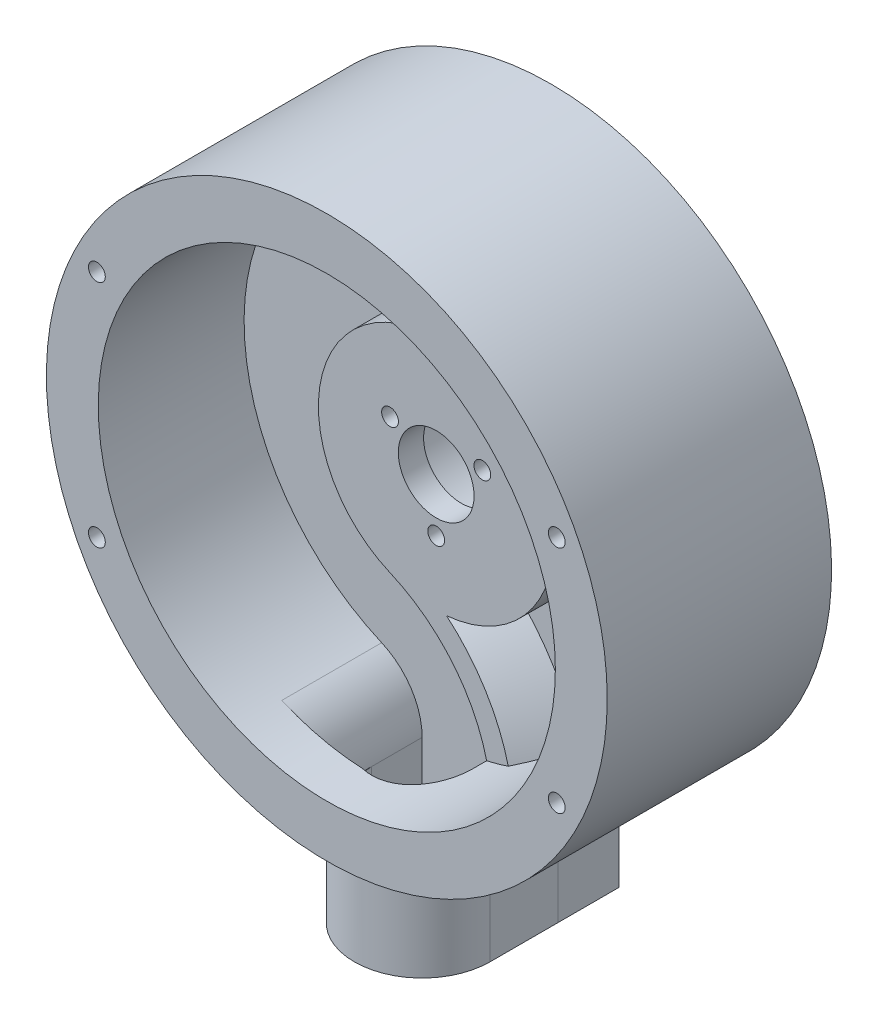
SolidWorks part; units mm, degrees
ref_plane "前视基准面" through (0, 0, 0) normal (0, 0, 1) x (1, 0, 0)
ref_plane "上视基准面" through (0, 0, 0) normal (0, 1, 0) x (1, 0, 0)
ref_plane "右视基准面" through (0, 0, 0) normal (1, 0, 0) x (0, 0, -1)
other "Configuration Table"
sketch "草图1" plane through (0, 0, 0) normal (0, 0, 1) x (1, 0, 0)
  circle A0 centre (0, 0) radius 21
  circle A1 centre (0, 0) radius 12.6
  dimension "D1" = 42
  dimension "D2" = 25.2
extrude "凸台-拉伸1" add sketch "草图1" along normal blind 7
sketch "草图3" plane through (0, 0, 0) normal (0, 0, -1) x (-1, 0, 0)
  circle A0 centre (0, 0) radius 50
  circle A2 centre (0, 0) radius 21
  circle A3 centre (0, 0) radius 21
  dimension "D2" = 100
  dimension "D1" = 0
extrude "凸台-拉伸3" add sketch "草图3" against normal blind 3
sketch "草图4" plane through (0, 0, 3) normal (0, 0, 1) x (1, 0, 0)
  circle A0 centre (0, 0) radius 40.75
  circle A1 centre (0, 0) radius 50
  circle A2 centre (0, 0) radius 50
  dimension "D2" = 81.5
  dimension "D1" = 0
extrude "凸台-拉伸4" add sketch "草图4" along normal blind 26
sketch "草图5" plane through (0, 0, 7) normal (0, 0, 1) x (1, 0, 0)
  circle A1 centre (0, 0) radius 6.75
  circle A3 centre (0, 0) radius 21
  circle A4 centre (0, 0) radius 21
  dimension "D1" = 13.5
  dimension "D2" = 0
extrude "凸台-拉伸5" add sketch "草图5" along normal blind 2.5
sketch "草图6" plane through (0, 0, 3) normal (0, 0, 1) x (1, 0, 0)
  arc A0 (-8.2952, -19.2922) -> (9, -39.7437) centre (-20.1456, -46.8525) cw
  circle A1 centre (0, 0) radius 21 construction
  circle A2 centre (0, 0) radius 21 construction
  circle A3 centre (0, 0) radius 40.75 construction
  arc A4 (0.3602, -20.9969) -> (11.9001, -38.9737) centre (-20.1456, -46.8525) cw
  circle A5 centre (0, 0) radius 40.75 construction
  circle A6 centre (0, 0) radius 40.75
  circle A7 centre (0, 0) radius 21
  circle A8 centre (0, 0) radius 21
  circle M2 centre (0, 0) radius 21
  circle M3 centre (0, 0) radius 40.75
  dimension "D2" = 30
  dimension "D3" = 33
  dimension "D1" = 9
  dimension "D4" = 0
extrude "凸台-拉伸6" add sketch "草图6" along normal blind 6.5 contours A4 A0 M2 M3 region at (4.9964, -29.2129, 3)
ref_plane "基准面1" through (0, -68, 0) normal (0, 1, 0) x (1, 0, 0)
sketch "草图7" plane through (0, -68, 0) normal (0, 1, 0) x (1, 0, 0)
  line L0 (50, 0) -> (-50, 0) construction
  line L1 (-9, -12) -> (9, -12)
  line L2 (-9, -12) -> (-9, -3)
  line L3 (-9, -3) -> (9, -3)
  line L4 (9, -12) -> (9, -3)
  line L5 (-9, -12) -> (9, -3) construction
  line L6 (-9, -3) -> (9, -12) construction
  arc A0 (-9, -12) -> (9, -12) centre (0, -12) ccw
  point P0 (0, -7.5)
  dimension "D2" = 9
  dimension "D1" = 3
  dimension "D3" = 9
extrude "切除-拉伸1" cut sketch "草图7" along normal up to surface (28.2563 mm away) contours L1 L4 L3 L2 | L1 A0 region at (0, -68, 7.5) region at (0, -68, 15.8197) up to face at (5.225, -19.6794, 6.25)
sketch "草图8" plane through (0, 0, 29) normal (0, 0, 1) x (1, 0, 0)
  line L1 (-41, -20.5) -> (41, -20.5) construction
  line L2 (-41, -20.5) -> (-41, 20.5) construction
  line L3 (-41, 20.5) -> (41, 20.5) construction
  line L4 (41, -20.5) -> (41, 20.5) construction
  line L5 (-41, -20.5) -> (41, 20.5) construction
  line L6 (-41, 20.5) -> (41, -20.5) construction
  circle A0 centre (-41, 20.5) radius 1.5
  circle A1 centre (41, 20.5) radius 1.5
  circle A2 centre (41, -20.5) radius 1.5
  circle A3 centre (-41, -20.5) radius 1.5
  point P0 (0, 0)
  dimension "D3" = 3
  dimension "D4" = 3
  dimension "D5" = 3
  dimension "D6" = 3
  dimension "D1" = 41
  dimension "D2" = 82
extrude "切除-拉伸2" cut sketch "草图8" against normal blind 5
chamfer "倒角1" distance 7.5 angle 45 1 edges at (7.625, -29.0257, 3)
sketch "草图12" plane through (0, 0, 0) normal (0, 0, -1) x (-1, 0, 0)
  circle A0 centre (0, 0) radius 40.75 construction
  circle A1 centre (0, 0) radius 50
  circle A2 centre (0, 0) radius 50
  circle A3 centre (0, 0) radius 40.75
  arc A4 (8.2952, -19.2922) -> (-1.8421, -20.9191) centre (0, 0) ccw construction
  arc A5 (8.2952, -19.2922) -> (-1.8421, -20.9191) centre (0, 0) ccw
  circle A6 centre (0, 0) radius 12.6 construction
  circle A7 centre (0, 0) radius 12.6
  arc A8 (8.2952, -19.2922) -> (-1.8421, -20.9191) centre (0, 0) cw
  circle M2 centre (0, 0) radius 12.6
  circle M3 centre (0, 0) radius 50
  dimension "D1" = 0
extrude "凸台-拉伸10" add sketch "草图12" along normal blind 11 contours A8 A5 M2 | A2 A3 M3 region at (48.5858, 0, 0) region at (-3.2334, -20.1482, 0)
sketch "草图13" plane through (0, 0, 9.5) normal (0, 0, 1) x (1, 0, 0)
  circle A0 centre (0, 0) radius 9.5 construction
  circle A1 centre (0, -9.5) radius 1.5
  circle A2 centre (8.2272, 4.75) radius 1.5
  circle A3 centre (-8.2272, 4.75) radius 1.5
  dimension "D1" = 19
  dimension "D2" = 3
  dimension "D3" = 3
  dimension "D4" = 3
  dimension "D5" = 120
extrude "切除-拉伸3" cut sketch "草图13" against normal blind 20
sketch "草图9" plane through (0, -68, 0) normal (0, 1, 0) x (1, 0, 0)
  line L0 (-9, -3) -> (-9, -12) construction
  line L1 (-9, -3) -> (9, -3) construction
  line L2 (9, -3) -> (9, -12) construction
  line L3 (-9, -3) -> (-9, -12)
  line L4 (-9, -3) -> (9, -3)
  line L5 (9, -3) -> (9, -12)
  line L6 (-12.1, 0.1) -> (-12.1, -12)
  line L7 (12.1, 0.1) -> (12.1, -12)
  line L8 (-9, 0.1) -> (9, 0.1)
  line L9 (-12.1, 0.1) -> (12.1, 0.1) construction
  line L11 (-12.1, 0.1) -> (-12.1, 11)
  line L12 (-12.1, 11) -> (-9, 11)
  line L13 (-9, 0.1) -> (-9, 11)
  line L15 (12.1, 0.1) -> (12.1, 11)
  line L16 (12.1, 11) -> (9, 11)
  line L17 (9, 0.1) -> (9, 11)
  arc A0 (-9, -12) -> (9, -12) centre (0, -12) ccw construction
  arc A1 (-9, -12) -> (9, -12) centre (0, -12) ccw
  arc A2 (-12.1, -12) -> (12.1, -12) centre (0, -12) ccw
  dimension "D2" = 10.9
  dimension "D3" = 10.9
  dimension "D1" = 3.1
extrude "凸台-拉伸11" add sketch "草图9" along normal up to next
ref_plane "基准面2" through (-50, 0, 0) normal (1, 0, 0) x (0, 0, -1)
sketch "草图14" plane through (-50, 0, 0) normal (1, 0, 0) x (0, 0, -1)
  circle A0 centre (7, -18) radius 3
  dimension "D3" = 6
  dimension "D1" = 18
  dimension "D2" = 7
extrude "切除-拉伸4" cut sketch "草图14" along normal blind 10
sketch "草图15" plane through (0, 0, -11) normal (0, 0, -1) x (-1, 0, 0)
  line L1 (-31.8198, 31.8198) -> (31.8198, 31.8198) construction
  line L2 (-31.8198, 31.8198) -> (-31.8198, -31.8198) construction
  line L3 (-31.8198, -31.8198) -> (31.8198, -31.8198) construction
  line L4 (31.8198, 31.8198) -> (31.8198, -31.8198) construction
  line L5 (-31.8198, 31.8198) -> (31.8198, -31.8198) construction
  line L6 (-31.8198, -31.8198) -> (31.8198, 31.8198) construction
  circle A0 centre (-31.8198, 31.8198) radius 1.25
  circle A1 centre (31.8198, 31.8198) radius 1.25
  circle A2 centre (31.8198, -31.8198) radius 1.25
  circle A3 centre (-31.8198, -31.8198) radius 1.25
  point P0 (0, 0)
  dimension "D2" = 2.5
  dimension "D3" = 2.5
  dimension "D4" = 2.5
  dimension "D5" = 2.5
  dimension "D1" = 90
extrude "切除-拉伸5" cut sketch "草图15" against normal blind 10
sketch "草图16" plane through (0, 0, 3) normal (0, 0, 1) x (1, 0, 0)
  line L2 (-9, -39.7437) -> (-0.1, -39.7437)
  line L3 (-9, -39.7437) -> (-9, -48.3897)
  line L4 (-9, -39.7437) -> (-9, -68)
  line L5 (-9, -68) -> (9, -68)
  line L6 (9, -68) -> (9, -39.7437)
  line L7 (-9, -39.7437) -> (-9, -68)
  line L8 (-9, -68) -> (9, -68)
  line L9 (9, -68) -> (9, -39.7437)
  line L10 (-9, -48.3897) -> (-0.1, -48.3897)
  line L11 (-0.1, -39.7437) -> (-0.1, -48.3897)
  arc A0 (-16.2227, -37.3816) -> (-9, -48.3897) centre (-21, -48.3897) cw
  arc A3 (9.1591, -18.8974) -> (-8.2952, -19.2922) centre (0, 0) ccw
  arc A6 (18.9013, -36.1013) -> (-9, -39.7437) centre (0, 0) ccw
  arc A10 (18.9013, -36.1013) -> (-9, -39.7437) centre (0, 0) ccw
  arc A17 (9.1591, -18.8974) -> (-8.2952, -19.2922) centre (0, 0) ccw
  arc A18 (18.9013, -36.1013) -> (9.1591, -18.8974) centre (-20.1456, -46.8525) ccw
  arc A19 (18.9013, -36.1013) -> (9.1591, -18.8974) centre (-20.1456, -46.8525) ccw
  arc A20 (9, -39.7437) -> (-8.2952, -19.2922) centre (-20.1456, -46.8525) ccw
  arc A21 (9, -39.7437) -> (-8.2952, -19.2922) centre (-20.1456, -46.8525) ccw
  arc M10 (18.9013, -36.1013) -> (-9, -39.7437) centre (0, 0) ccw
  line M11 (-9, -39.7437) -> (-9, -68)
  dimension "D2" = 12
  dimension "D3" = 8.9
  dimension "D1" = 0
extrude "切除-拉伸6" cut sketch "草图16" along normal blind 17.8 contours A0 M10 M11 | L3 L2 L11 L10 region at (-10.5758, -41.221, 3)
sketch "草图17" plane through (0, 0, 7) normal (0, 0, -1) x (-1, 0, 0)
  circle A0 centre (0, -9.5) radius 1.5 construction
  circle A1 centre (0, 0) radius 12.6
  circle A2 centre (0, 0) radius 12.6
  circle A3 centre (8.2272, 4.75) radius 1.5 construction
  circle A4 centre (-8.2272, 4.75) radius 1.5 construction
  circle A5 centre (0, 0) radius 6.75 construction
  circle A6 centre (0, -9.5) radius 1.5
  circle A7 centre (8.2272, 4.75) radius 1.5
  circle A8 centre (-8.2272, 4.75) radius 1.5
  circle A9 centre (0, 0) radius 6.75
  dimension "D1" = 0
extrude "凸台-拉伸12" add sketch "草图17" along normal blind 2
